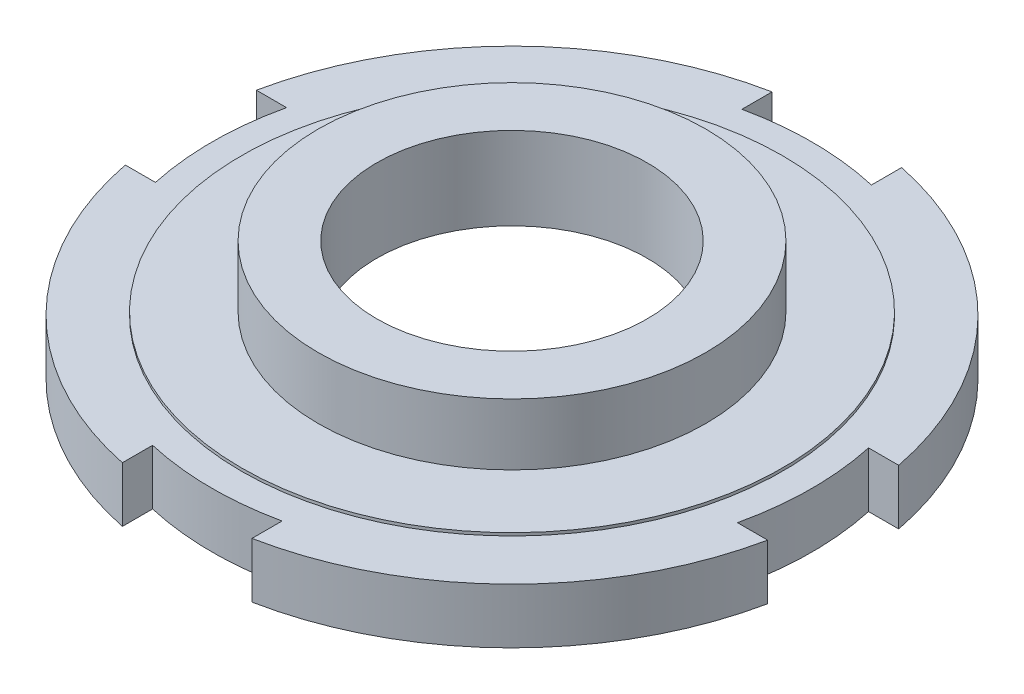
SolidWorks part; units mm, degrees
ref_plane "Front Plane" through (0, 0, 0) normal (0, 0, 1) x (1, 0, 0)
ref_plane "Top Plane" through (0, 0, 0) normal (0, 1, 0) x (1, 0, 0)
ref_plane "Right Plane" through (0, 0, 0) normal (1, 0, 0) x (0, 0, -1)
sketch "Sketch1" plane through (0, 0, 0) normal (0, 1, 0) x (1, 0, 0)
  line L0 (30.2899, 6.5405) -> (33.4017, 6.5405)
  line L1 (30.2051, -6.9215) -> (33.3248, -6.9215)
  line L2 (-55, 0) -> (55, 0) construction
  line L3 (6.5405, -30.2899) -> (6.5405, -33.4017)
  line L4 (-6.9215, -30.2051) -> (-6.9215, -33.3248)
  line L5 (-30.2899, -6.5405) -> (-33.4017, -6.5405)
  line L6 (-30.2051, 6.9215) -> (-33.3248, 6.9215)
  line L7 (-6.5405, 30.2899) -> (-6.5405, 33.4017)
  line L8 (6.9215, 30.2051) -> (6.9215, 33.3248)
  arc A1 (-33.4017, -6.5405) -> (-6.9215, -33.3248) centre (0, 0) ccw
  circle A2 centre (0, 0) radius 13.97
  arc A3 (-30.2051, 6.9215) -> (-30.2899, -6.5405) centre (0, 0) ccw
  arc A4 (6.9215, 30.2051) -> (-6.5405, 30.2899) centre (0, 0) ccw
  arc A5 (30.2051, -6.9215) -> (30.2899, 6.5405) centre (0, 0) ccw
  arc A6 (-6.9215, -30.2051) -> (6.5405, -30.2899) centre (0, 0) ccw
  arc A7 (6.5405, -33.4017) -> (33.3248, -6.9215) centre (0, 0) ccw
  arc A8 (33.4017, 6.5405) -> (6.9215, 33.3248) centre (0, 0) ccw
  arc A9 (-6.5405, 33.4017) -> (-33.3248, 6.9215) centre (0, 0) ccw
  point P26 (0, 0)
  dimension "D1" = 68.072
  dimension "D2" = 61.976
  dimension "D6" = 27.94
  dimension "D3" = 13.462
  dimension "D4" = 6.5405
  dimension "D5" = 4
ref_axis "Axis1" through (41.3265, 0, 0) along (-1, 0, 0)
ref_plane "Plane2" through (0, 0, 0) normal (0, -0.9903, 0.1392) x (-1, 0, 0)
ref_plane "Plane3" through (0, 6.2882, -0.8837) normal (0, -0.9903, 0.1392) x (-1, 0, 0)
extrude "Boss-Extrude2" add sketch "Sketch1" along normal blind 6
sketch "Sketch2" plane through (0, 0, 0) normal (0, -1, 0) x (1, 0, 0)
  line L3 (17.3777, -10.033) -> (-0.2866, -40.6283)
  line L4 (-4.5397, -40.3749) -> (8.1962, -18.3157)
  line L5 (3.2131, 0) -> (-3.2131, 0) construction
  arc A3 (8.1962, -18.3157) -> (17.3777, -10.033) centre (0, 0) cw
  arc A4 (-0.2866, -40.6283) -> (-4.5397, -40.3749) centre (0, 0) cw
  point P4 (8.5456, -25.3307)
  dimension "D1" = 20.066
  dimension "D2" = 3.81
  dimension "D3" = 60
extrude "Cut-Extrude1" cut sketch "Sketch2" against normal blind 3.81
sketch "Sketch3" plane through (0, 0, 0) normal (0, -1, 0) x (1, 0, 0)
  circle A0 centre (0, 0) radius 27.94
  dimension "D1" = 55.88
extrude "Cut-Extrude2" cut sketch "Sketch3" against normal blind 0.3
sketch "Sketch5" plane through (0, 6, 0) normal (0, 1, 0) x (1, 0, 0)
  circle A0 centre (0, 0) radius 20.01
  circle A1 centre (0, 0) radius 13.97 construction
  circle A2 centre (0, 0) radius 13.97
  dimension "D1" = 40.02
extrude "Boss-Extrude3" add sketch "Sketch5" along normal blind 6.35
sketch "Sketch6" plane through (0, 6, 0) normal (0, 1, 0) x (1, 0, 0)
  circle A0 centre (0, 0) radius 27.94
  circle A3 centre (0, 0) radius 50.8
  dimension "D1" = 55.88
  dimension "D2" = 101.6
extrude "Cut-Extrude3" cut sketch "Sketch6" against normal blind 0.3
